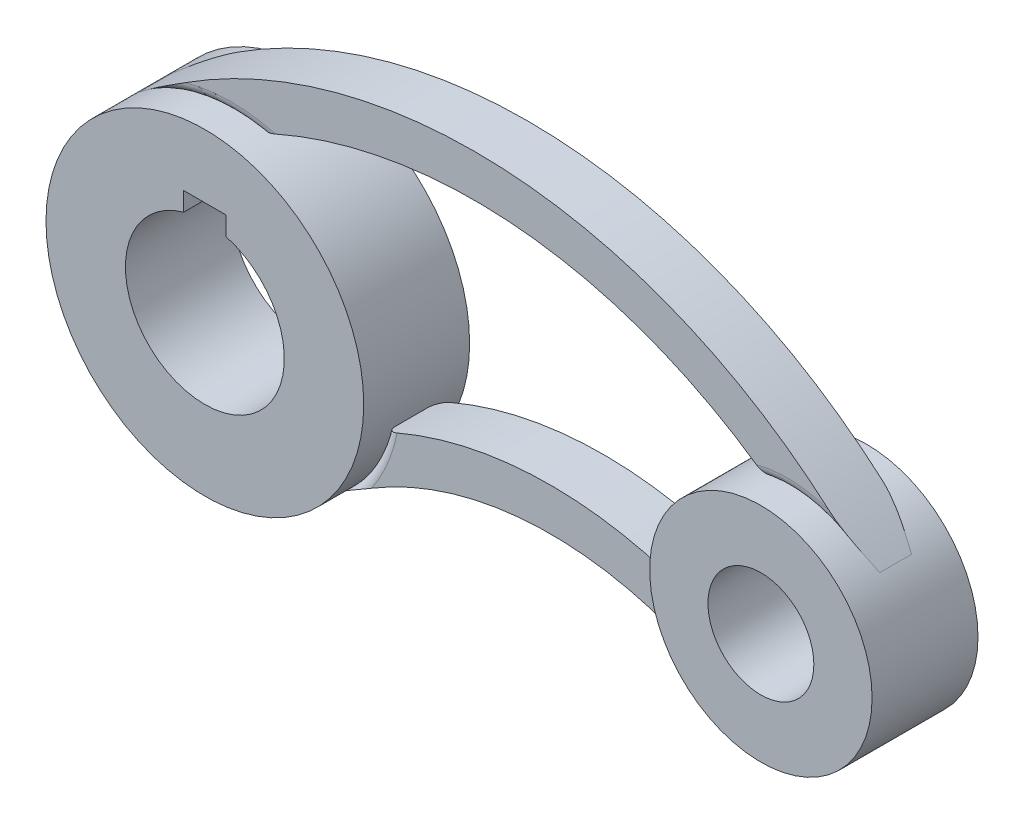
SolidWorks part; units mm, degrees
material "1060-H14"
ref_plane "Ön Düzlem" through (0, 0, 0) normal (0, 0, 1) x (1, 0, 0)
ref_plane "Üst Düzlem" through (0, 0, 0) normal (0, 1, 0) x (1, 0, 0)
ref_plane "Sağ Düzlem" through (0, 0, 0) normal (1, 0, 0) x (0, 0, -1)
sketch "Çizim1" plane through (0, 0, 0) normal (0, 0, 1) x (1, 0, 0)
  line L0 (-441.5374, 4.6763) -> (608.4626, 4.6763) construction
  line L2 (-481.5374, 184.6763) -> (-401.5374, 184.6763)
  line L3 (-481.5374, 184.6763) -> (-481.5374, 149.2446)
  line L5 (-401.5374, 149.2446) -> (-401.5374, 184.6763)
  circle A0 centre (-441.5374, 4.6763) radius 300
  circle A1 centre (608.4626, 4.6763) radius 210
  arc A2 (-481.5374, 149.2446) -> (-401.5374, 149.2446) centre (-441.5374, 4.6763) ccw
  circle A3 centre (608.4626, 4.6763) radius 100
  arc A4 (-635.3826, 233.6392) -> (762.9087, 146.9661) centre (18.5705, -538.7863) cw
  arc A5 (-251.9125, -227.794) -> (499.7711, -175.0072) centre (161.3624, -734.4478) cw
  arc A6 (-388.1215, 299.8825) -> (571.6869, 211.431) centre (18.5705, -538.7863) cw
  arc A7 (-151.0999, -70.464) -> (403.6643, -41.7741) centre (161.3624, -734.4478) cw
  arc A9 (-302.4792, -165.8019) -> (541.1774, -106.5564) centre (161.3624, -734.4478) cw construction
  arc A10 (-583.6905, 172.5824) -> (704.0721, 92.7605) centre (18.5705, -538.7863) cw construction
  point P28 (-441.5374, 184.6763)
  dimension "D1" = 600
  dimension "D2" = 420
  dimension "D4" = 300
  dimension "D5" = 200
  dimension "D6" = 80
  dimension "D7" = 80
extrude "Yükseklik-Ekstrüzyon1" add sketch "Çizim1" along normal mid plane 200 contours A0 A2 L3 L2 L5 | A1 A3 region at (-152.355, -32.1257, 0) region at (673.651, 198.044, 0)
extrude "Yükseklik-Ekstrüzyon2" add sketch "Çizim1<3>" along normal mid plane 100 separate body contours A0 A6 A1 A4 | A7 A0 A5 A1 region at (-522.8878, 308.3265, 0) region at (122.3425, -67.6383, 0)
sketch "Çizim1<3>" plane through (0, 0, 0) normal (0, 0, 1) x (1, 0, 0) same geometry as "Çizim1"
fillet "Radyus1" radius 20 4 edges at (675.5485, 203.6725, -50) (675.5485, 203.6725, 50) (-519.1721, 294.457, -50) (-519.1721, 294.457, 50)
fillet "Radyus2" radius 20 4 edges at (438.149, -118.1784, 50) (438.149, -118.1784, -50) (-188.9445, -157.1782, -50) (-188.9445, -157.1782, 50)
